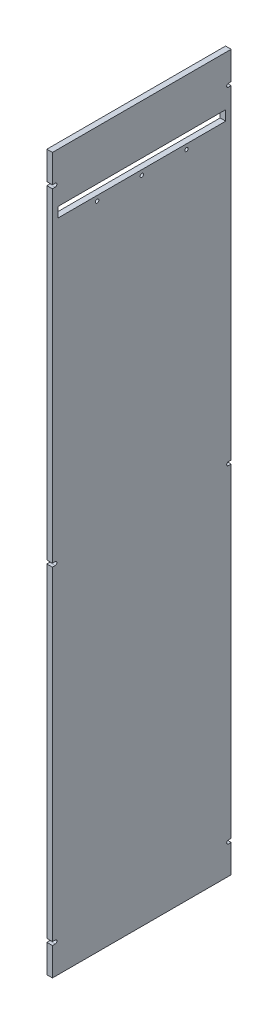
SolidWorks part; units mm, degrees
ref_plane "Front Plane" through (0, 0, 0) normal (0, 0, 1) x (1, 0, 0)
ref_plane "Top Plane" through (0, 0, 0) normal (0, 1, 0) x (1, 0, 0)
ref_plane "Right Plane" through (0, 0, 0) normal (1, 0, 0) x (0, 0, -1)
sketch "Sketch1" plane through (0, 0, 0) normal (0, 1, 0) x (1, 0, 0)
  line L1 (0, 0) -> (4.7625, 0)
  line L2 (0, 0) -> (0, 152.4)
  line L3 (0, 152.4) -> (4.7625, 152.4)
  line L4 (4.7625, 0) -> (4.7625, 152.4)
  dimension "D1" = 152.4
  dimension "D2" = 4.7625
extrude "Boss-Extrude1" add sketch "Sketch1" along normal blind 609.6
sketch "Sketch2" plane through (4.7625, 0, 0) normal (1, 0, 0) x (0, 0, -1)
  line L0 (0, 609.6) -> (152.4, 609.6) construction
  line L1 (147.7645, 558.8) -> (4.6355, 558.8)
  line L2 (147.7645, 558.8) -> (147.7645, 567.309)
  line L3 (147.7645, 567.309) -> (4.6355, 567.309)
  line L4 (4.6355, 558.8) -> (4.6355, 567.309)
  line L5 (76.2, 609.6) -> (76.2, 527.6475) construction
  line L6 (152.4, 609.6) -> (152.4, 0) construction
  dimension "D1" = 8.509
  dimension "D2" = 143.129
  dimension "D3" = 42.291
  dimension "D4" = 4.6355
extrude "Cut-Extrude1" cut sketch "Sketch2" against normal through all
hole_wizard "#4 Clearance Hole1" positions "Sketch9" profile "Sketch10" hole size "#4" standard "ANSI Inch" end condition through all
sketch "Sketch9" plane through (4.7625, 0, 0) normal (1, 0, 0) x (0, 0, -1)
  line L2 (76.2, 609.6) -> (76.2, 510.9761) construction
  line L3 (0, 609.6) -> (152.4, 609.6) construction
  line L4 (4.6355, 558.8) -> (147.7645, 558.8) construction
  line L5 (76.2, 554.5455) -> (38.1, 554.5455) construction
  line L7 (76.2, 554.5455) -> (114.3, 554.5455) construction
  point P17 (76.2, 554.5455)
  point P24 (38.1, 554.5455)
  point P29 (114.3, 554.5455)
  dimension "D1" = 4.2545
  dimension "D2" = 38.1
  dimension "D3" = 38.1
sketch "Sketch10" plane through (4.7625, 554.5455, -114.3) normal (0, 1, 0) x (0, 0, -1)
  line L0 (0, 0) -> (0, 4.7625)
  line L1 (0, 4.7625) -> (1.4732, 4.7625)
  line L2 (1.4732, 4.7625) -> (1.4732, 0)
  line L5 (1.4732, 0) -> (0, 0)
  line L11 (0, -6.35) -> (0, 107.95) construction
  dimension "Thru Hole Dia." = 2.9464
  dimension "Thru Hole Depth" = 4.7625
sketch "Sketch12" plane through (4.7625, 0, 0) normal (1, 0, 0) x (0, 0, -1)
  line L0 (150.0188, 0) -> (150.0188, 609.6) construction
  line L1 (0, 0) -> (152.4, 0) construction
  line L2 (0, 609.6) -> (152.4, 609.6) construction
  line L3 (2.3813, 0) -> (2.3813, 609.6) construction
  line L4 (152.4, 609.6) -> (152.4, 0) construction
  line L5 (0, 609.6) -> (0, 0) construction
  line L6 (152.4, 25.4) -> (0, 25.4) construction
  line L7 (150.0188, 23.9395) -> (152.4, 23.9395)
  line L8 (150.0188, 26.8605) -> (152.4, 26.8605)
  line L9 (152.4, 23.9395) -> (152.4, 26.8605)
  line L10 (2.3812, 23.9395) -> (0, 23.9395)
  line L11 (2.3812, 26.8605) -> (0, 26.8605)
  line L12 (0, 23.9395) -> (0, 26.8605)
  line L13 (0, 303.3395) -> (0, 306.2605)
  line L14 (2.3812, 303.3395) -> (0, 303.3395)
  line L15 (2.3812, 306.2605) -> (0, 306.2605)
  line L16 (152.4, 303.3395) -> (152.4, 306.2605)
  line L17 (150.0188, 303.3395) -> (152.4, 303.3395)
  line L18 (150.0188, 306.2605) -> (152.4, 306.2605)
  line L19 (0, 582.7395) -> (0, 585.6605)
  line L20 (2.3812, 582.7395) -> (0, 582.7395)
  line L21 (2.3812, 585.6605) -> (0, 585.6605)
  line L22 (152.4, 582.7395) -> (152.4, 585.6605)
  line L23 (150.0188, 582.7395) -> (152.4, 582.7395)
  line L24 (150.0188, 585.6605) -> (152.4, 585.6605)
  arc A0 (150.0188, 26.8605) -> (150.0188, 23.9395) centre (150.0188, 25.4) ccw
  arc A1 (2.3812, 23.9395) -> (2.3812, 26.8605) centre (2.3812, 25.4) ccw
  arc A2 (2.3812, 303.3395) -> (2.3812, 306.2605) centre (2.3812, 304.8) ccw
  arc A3 (150.0188, 306.2605) -> (150.0188, 303.3395) centre (150.0188, 304.8) ccw
  arc A4 (2.3812, 582.7395) -> (2.3812, 585.6605) centre (2.3812, 584.2) ccw
  arc A5 (150.0188, 585.6605) -> (150.0188, 582.7395) centre (150.0188, 584.2) ccw
  dimension "D4" = 3
  dimension "D1" = 2.3813
  dimension "D2" = 2.3813
  dimension "D3" = 25.4
extrude "Cut-Extrude2" cut sketch "Sketch12" against normal through all
